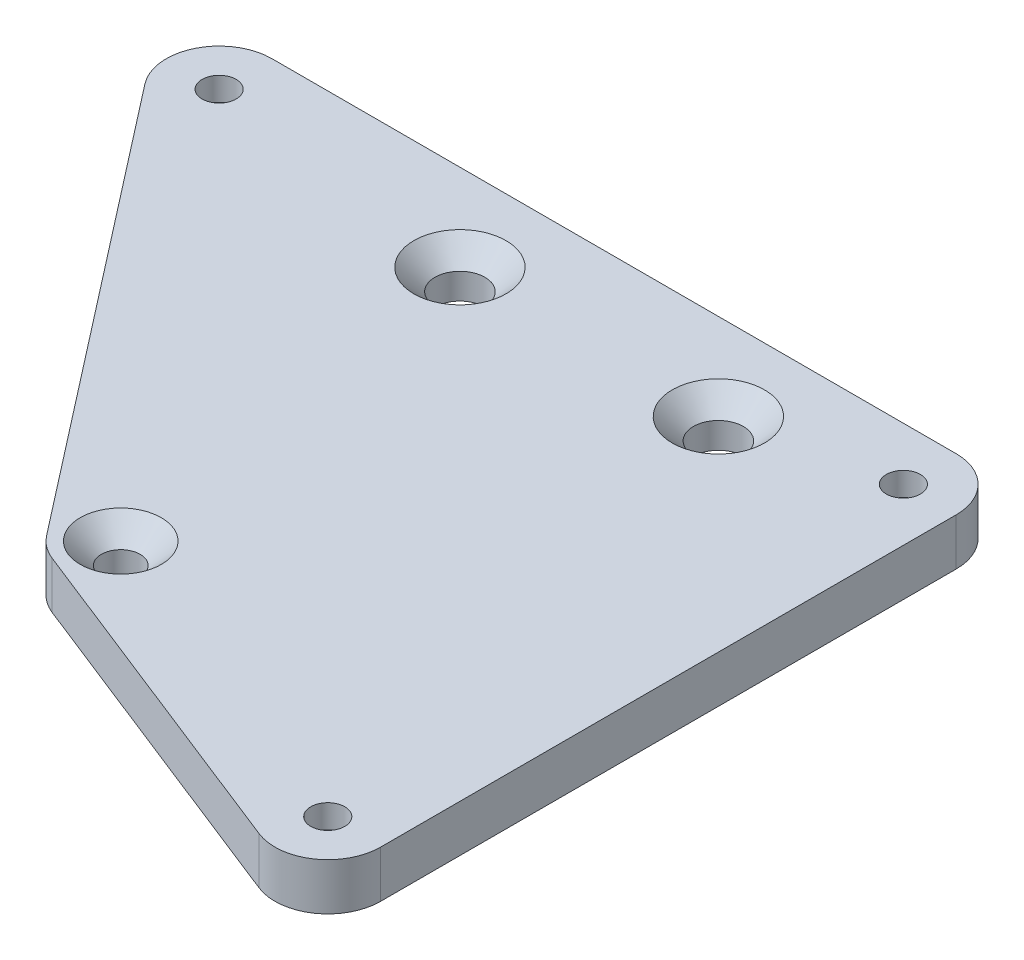
SolidWorks part; units mm, degrees
ref_plane "Front Plane" through (0, 0, 0) normal (0, 0, 1) x (1, 0, 0)
ref_plane "Top Plane" through (0, 0, 0) normal (0, 1, 0) x (1, 0, 0)
ref_plane "Right Plane" through (0, 0, 0) normal (1, 0, 0) x (0, 0, -1)
sketch "Sketch1" plane through (0, 0, 0) normal (0, 1, 0) x (1, 0, 0)
  line L0 (-32.679, 21.7397) -> (-3.554, -15.7603)
  line L5 (-1.6527, -17.1855) -> (27.4723, -28.6855)
  line L6 (33.625, -24.5) -> (33.625, 24.5)
  line L7 (29.125, 29) -> (-29.125, 29)
  circle A0 centre (16.25, 21.625) radius 2.125 construction
  circle A1 centre (-5.75, 21.625) radius 2.125 construction
  circle A2 centre (16.25, 21.625) radius 2.125
  circle A3 centre (-5.75, 21.625) radius 2.125
  circle A4 centre (0, -13) radius 1.65 construction
  circle A5 centre (0, -13) radius 1.65
  circle A6 centre (-29.125, 24.5) radius 1.45 construction
  circle A7 centre (29.125, 24.5) radius 1.45 construction
  circle A8 centre (29.125, -24.5) radius 1.45 construction
  circle A9 centre (-29.125, 24.5) radius 1.45
  circle A10 centre (29.125, 24.5) radius 1.45
  circle A11 centre (29.125, -24.5) radius 1.45
  arc A12 (-3.554, -15.7603) -> (-1.6527, -17.1855) centre (0, -13) ccw
  arc A13 (27.4723, -28.6855) -> (33.625, -24.5) centre (29.125, -24.5) ccw
  arc A14 (33.625, 24.5) -> (29.125, 29) centre (29.125, 24.5) ccw
  arc A15 (-29.125, 29) -> (-32.679, 21.7397) centre (-29.125, 24.5) ccw
  circle A16 centre (29.125, -24.5) radius 3
  circle A17 centre (-29.125, 24.5) radius 3
  circle A18 centre (29.125, 24.5) radius 3
  dimension "D1" = 4.5
  dimension "D2" = 6
extrude "Boss-Extrude1" add sketch "Sketch1" against normal blind 4 contours L7 A15 L0 A12 L5 A13 L6 A14 A18 A17 A16 A2 A3 A5 region at (7.2053, 0, -5.5004)
extrude "Boss-Extrude2" add sketch "Sketch1<3>" against normal blind 2 contours A16 A11 | A17 A9 | A18 A10 region at (26.2099, 0, 24.5) region at (-32.0401, 0, -24.5) region at (26.2099, 0, -24.5)
sketch "Sketch1<3>" plane through (0, 0, 0) normal (0, 1, 0) x (1, 0, 0) same geometry as "Sketch1"
chamfer "Chamfer1" distance 1.8 angle 45 3 edges at (-5.75, 0, -19.5) (16.25, 0, -19.5) (0, 0, 14.65)
